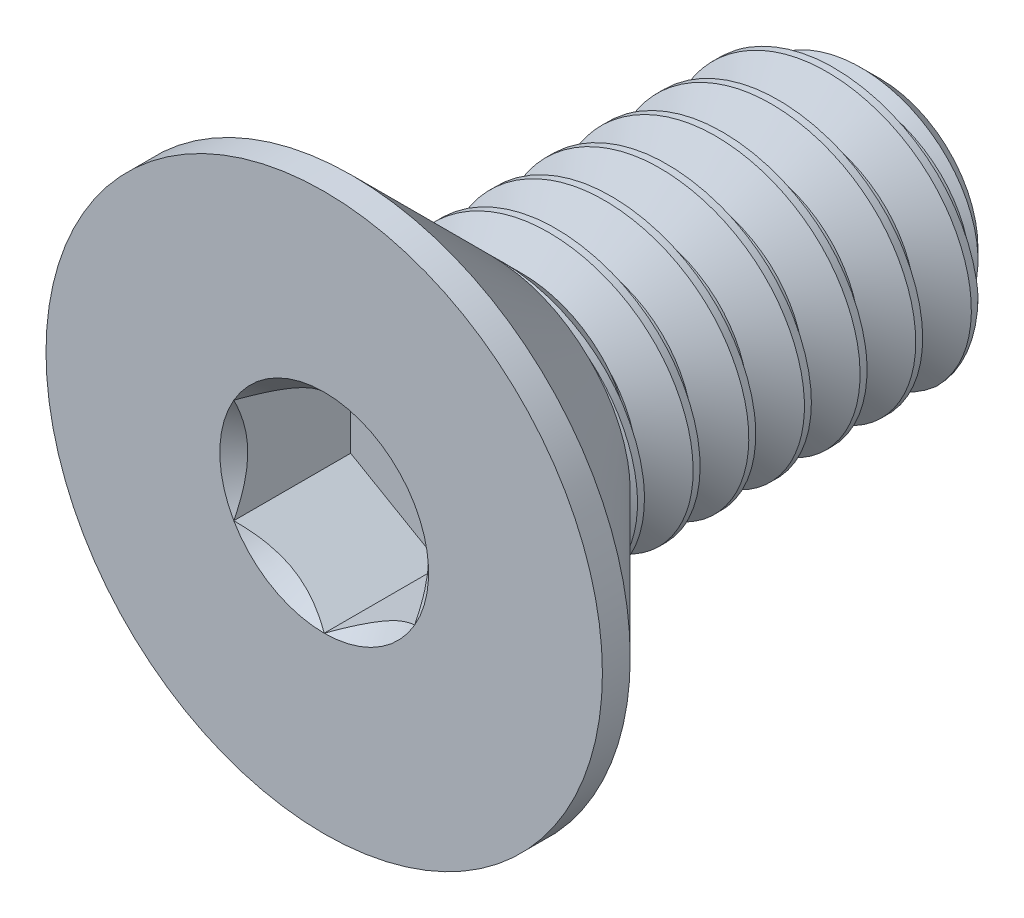
SolidWorks part; units mm, degrees
ref_plane "Front" through (0, 0, 0) normal (0, 0, 1) x (1, 0, 0)
ref_plane "Top" through (0, 0, 0) normal (0, 1, 0) x (1, 0, 0)
ref_plane "Right" through (0, 0, 0) normal (1, 0, 0) x (0, 0, -1)
sketch "Sketch1" plane through (0, 0, 0) normal (1, 0, 0) x (0, 0, -1)
  line L0 (0, 2) -> (0.2, 2) construction
  line L1 (0.2, 2) -> (1.2, 1) construction
  line L2 (0, 1) -> (4, 1)
  line L3 (4, 1) -> (4, 0)
  line L4 (4, 0) -> (0, 0)
  line L5 (0, 0) -> (0, 2) construction
  line L6 (0, 2) -> (0, -2) construction
  line L7 (4, 1) -> (4, -1) construction
  line L8 (0, -2) -> (0.2, -2) construction
  line L9 (0.2, -2) -> (1.2, -1) construction
  line L11 (0, 1) -> (0, 0)
  line L12 (1.2, 1) -> (1.2, 0) construction
revolve "Revolve1" add sketch "Sketch1" angle 360 mid plane about L4
sketch "Sketch3" plane through (0, 0, -4) normal (0, 0, -1) x (-1, 0, 0)
  circle A0 centre (0, 0) radius 1
curve "Helix/Spiral1" pitch 0.4 height 4 radius 1 centre (0, 0, -4) axis (0, 0, 1) start towards (0, 1, 0)
sketch "Sketch2" plane through (0, 0, 0) normal (1, 0, 0) x (0, 0, -1)
  line L0 (4, 1) -> (4.35, 1)
  line L1 (4.35, 1) -> (4.2, 0.7402)
  line L2 (4.2, 0.7402) -> (4.15, 0.7402)
  line L3 (4.15, 0.7402) -> (4, 1)
  line L4 (4.075, 0.8701) -> (4.275, 0.8701) construction
  dimension "D1" = 60
  dimension "D2" = 0.05
  dimension "D3" = 0.2
chamfer "Chamfer1" distance 0.3 angle 45 1 edges at (0, 1, -4)
sweep "Cut-Sweep1" cut profiles "Sketch2" path "Helix/Spiral1" align with end faces yes
sketch "Sketch7" plane through (0, 0, 0) normal (1, 0, 0) x (0, 0, -1)
  line L0 (0, 2) -> (0.2, 2) construction
  line L1 (0.2, 2) -> (1.2, 1) construction
  line L2 (0, 2) -> (0.2, 2)
  line L3 (0.2, 2) -> (1.2, 1)
  line L4 (1.2, 1) -> (1.2, 0) construction
  line L5 (1.2, 1) -> (1.2, 0)
  line L7 (0, 0) -> (0, 2) construction
  line L8 (0, 0) -> (0, 2)
  line L9 (0, 0) -> (1.2, 0)
  line L10 (2.2, 0) -> (-2.2, 0) construction
revolve "Revolve2" add sketch "Sketch7" angle 360 mid plane about L9
ref_plane "Plane1" through (0, 0, -1.2) normal (0, 0, 1) x (1, 0, 0)
sketch "Sketch8" plane through (0, 0, -1.2) normal (0, 0, 1) x (1, 0, 0)
  circle A0 centre (0, 0) radius 1
extrude "Boss-Extrude1" add sketch "Sketch8" against normal through all draft 45
sketch "Sketch5" plane through (0, 0, 0) normal (0, 0, 1) x (1, 0, 0)
  line L1 (0.65, -0.3753) -> (0.65, 0.3753)
  line L2 (0.65, 0.3753) -> (0, 0.7506)
  line L3 (0, 0.7506) -> (-0.65, 0.3753)
  line L4 (-0.65, 0.3753) -> (-0.65, -0.3753)
  line L5 (-0.65, -0.3753) -> (0, -0.7506)
  line L6 (0, -0.7506) -> (0.65, -0.3753)
  circle A0 centre (0, 0) radius 0.65 construction
  dimension "Hex" = 1.3
extrude "Cut-Extrude2" cut sketch "Sketch5" against normal blind 0.84
sketch "Sketch6" plane through (0, 0, 0) normal (0, 0, 1) x (1, 0, 0)
  circle A0 centre (0, 0) radius 0.7506
extrude "Cut-Extrude3" cut sketch "Sketch6" against normal blind 0.84 draft 45
sketch "Sketch9" [suppressed] plane through (0, 0, -5.5) normal (0, 0, 1) x (1, 0, 0)
  circle A1 centre (0, 0) radius 5
  circle A2 centre (0, 0) radius 5
  point P0 (0, 5)
  dimension "D1" = 0
extrude "Boss-Extrude2" [suppressed] add sketch "Sketch9" against normal offset from surface (18.5 mm away) 26 up to face at (0, 0.7, -4)
fillet "Fillet1" [suppressed] radius 0.2
sketch "Sketch10" plane through (0, 0, 0) normal (1, 0, 0) x (0, 0, -1)
  line L0 (4, 1) -> (4, -1) construction
  point P0 (3.4, -1)
  dimension "D1" = 0.6
equation "\"D3@Helix/Spiral1\" = \"Lg@Sketch1\""
equation "\"D2@Sketch2\" = \"D4@Helix/Spiral1\" * .125"
equation "\"D3@Sketch2\" = \"D4@Helix/Spiral1\" * .5"
equation "\"D1@Chamfer1\" = \"D4@Helix/Spiral1\" * .75"
equation "\"D1@Cut-Extrude2\" = \"Head Ht@Sketch1\" * .7"
equation "\"D1@Sketch10\" = \"D4@Helix/Spiral1\" * 1.5"
equation "\"D1@Cut-Extrude3\" = \"D1@Cut-Extrude2\""
equation "\"D1@Fillet1\" = \"Dia@Sketch1\" * .1"
